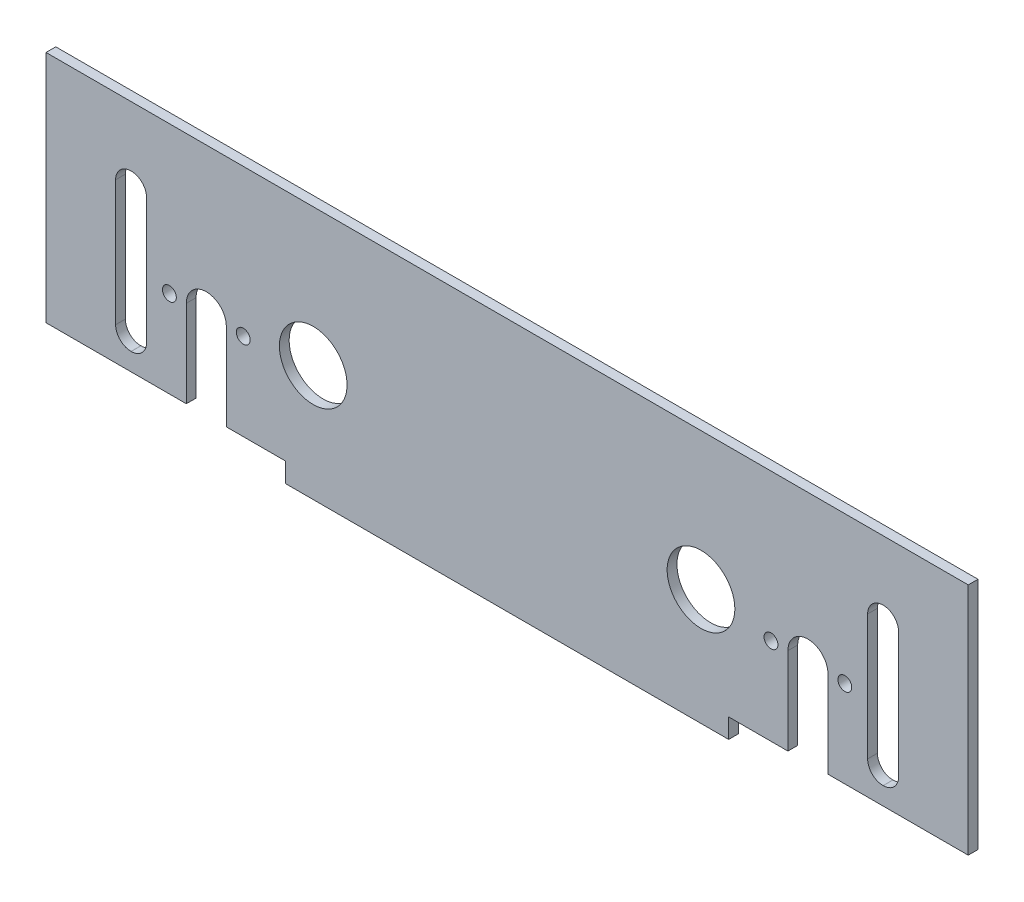
SolidWorks part; units mm, degrees
material "ABS"
ref_plane "X-Y Datum" through (0, 0, 0) normal (0, 0, 1) x (1, 0, 0)
ref_plane "X-Z Datum" through (0, 0, 0) normal (0, 1, 0) x (1, 0, 0)
ref_plane "Y-Z Datum" through (0, 0, 0) normal (1, 0, 0) x (0, 0, -1)
sketch "Sketch1" plane through (0, 0, 0) normal (0, 0, 1) x (1, 0, 0)
  line L1 (-149.85, 38.0375) -> (149.85, 38.0375)
  line L2 (-149.85, 38.0375) -> (-149.85, -38.0375)
  line L3 (-149.85, -38.0375) -> (149.85, -38.0375)
  line L4 (149.85, 38.0375) -> (149.85, -38.0375)
  line L5 (-149.85, 38.0375) -> (149.85, -38.0375) construction
  line L6 (-149.85, -38.0375) -> (149.85, 38.0375) construction
  point P0 (0, 0)
  dimension "D1" = 76.075
  dimension "D2" = 299.7
extrude "Boss-Extrude1" add sketch "Sketch1" along normal blind 3.175
sketch "Sketch3" plane through (0, 0, 0) normal (0, 0, -1) x (-1, 0, 0)
  line L3 (149.85, -38.0375) -> (-149.85, -38.0375) construction
  line L4 (149.85, -38.0375) -> (-149.85, -38.0375)
  line L5 (-104.25, -9.7625) -> (-104.25, -38.0375)
  line L6 (-91.25, -9.7625) -> (-91.25, -38.0375)
  line L7 (104.25, -9.7625) -> (104.25, -38.0375)
  line L8 (91.25, -9.7625) -> (91.25, -38.0375)
  circle A6 centre (-97.75, -9.7625) radius 6.5
  circle A7 centre (97.75, -9.7625) radius 6.5
  point P0 (97.75, -9.7625)
  point P1 (-97.75, -9.7625)
  point P16 (109.75, -9.7625)
  point P17 (85.75, -9.7625)
  point P18 (-85.75, -9.7625)
  point P19 (-109.75, -9.7625)
  dimension "D1" = 13
sketch "Sketch8" plane through (0, 0, 3.175) normal (0, 0, 1) x (1, 0, 0)
  line L1 (122.1609, 18.5125) -> (122.2247, 18.5125)
  line L4 (122.1928, -32.2824) -> (122.1928, 18.5125) construction
  line L5 (122.1609, -32.2824) -> (122.2247, -32.2824)
  line L6 (117.1609, -27.2824) -> (117.1609, 13.5125)
  line L8 (127.2247, -27.2824) -> (127.2247, 13.5125)
  line L9 (117.1609, -32.2824) -> (127.2247, 18.5125) construction
  line L10 (117.1609, 18.5125) -> (127.2247, -32.2824) construction
  arc A0 (122.1609, -32.2824) -> (117.1609, -27.2824) centre (122.1609, -27.2824) cw
  arc A1 (122.2247, -32.2824) -> (127.2247, -27.2824) centre (122.2247, -27.2824) ccw
  arc A2 (127.2247, 13.5125) -> (122.2247, 18.5125) centre (122.2247, 13.5125) ccw
  arc A3 (122.1609, 18.5125) -> (117.1609, 13.5125) centre (122.1609, 13.5125) ccw
  point P0 (122.1928, -6.885)
  dimension "D1" = 5
extrude "Cut-Extrude4" cut sketch "Sketch8" against normal through all
mirror "Mirror3" about plane through (0, 0, 0) normal (1, 0, 0) of "Cut-Extrude4"
extrude "Cut-Extrude5" cut sketch "Sketch3" against normal through all contours A6 | A6 L5 L4 L6 | A7 | A7 L8 L4 L7 region at (97.75, -26.4071, 0) region at (-97.75, -26.4071, 0) region at (-97.75, -9.7625, 0) region at (97.75, -9.7625, 0)
hole_wizard "M4 Clearance Hole1" positions "Sketch11" profile "Sketch10" hole size "M4" standard "ANSI Metric" end condition through all
sketch "Sketch11" plane through (0, 0, 0) normal (0, 0, -1) x (-1, 0, 0)
  point P0 (-85.75, -9.7625)
  point P3 (-109.75, -9.7625)
  point P6 (109.75, -9.7625)
  point P9 (85.75, -9.7625)
sketch "Sketch10" plane through (85.75, -9.7625, 0) normal (1, 0, 0) x (0, 1, 0)
  line L0 (0, 0) -> (0, 3.175)
  line L1 (0, 3.175) -> (2.25, 3.175)
  line L2 (2.25, 3.175) -> (2.25, 0)
  line L5 (2.25, 0) -> (0, 0)
  line L11 (0, -6.35) -> (0, 107.95) construction
  dimension "Thru Hole Dia." = 4.5
  dimension "Thru Hole Depth" = 3.175
sketch "Sketch12" plane through (0, -38.0375, 0) normal (0, -1, 0) x (1, 0, 0)
  line L0 (0, 0) -> (0, 3.175) construction
  line L1 (-91.25, 0) -> (91.25, 0) construction
  line L2 (-91.25, 3.175) -> (91.25, 3.175) construction
  line L4 (-72, 3.175) -> (72, 3.175)
  line L5 (-72, 3.175) -> (-72, 0)
  line L6 (-72, 0) -> (72, 0)
  line L7 (72, 3.175) -> (72, 0)
  line L8 (-72, 3.175) -> (72, 0) construction
  line L9 (-72, 0) -> (72, 3.175) construction
  point P6 (0, 1.5875)
  dimension "D1" = 144
extrude "Boss-Extrude2" add sketch "Sketch12" along normal blind 6.35
sketch "Sketch13" plane through (0, 0, 0) normal (0, 0, -1) x (-1, 0, 0)
  line L0 (65.2939, -6.6447) -> (60.7239, -6.6447) construction
  line L1 (65.2939, -2.7997) -> (65.2939, -10.4897) construction
  line L2 (60.7239, -10.7897) -> (60.7239, -2.4997) construction
  circle A0 centre (63.0089, -6.6447) radius 11
  dimension "D1" = 22
extrude "Cut-Extrude6" cut sketch "Sketch13" against normal through all
mirror "Mirror4" about plane through (0, 0, 0) normal (1, 0, 0) of "Cut-Extrude6"
